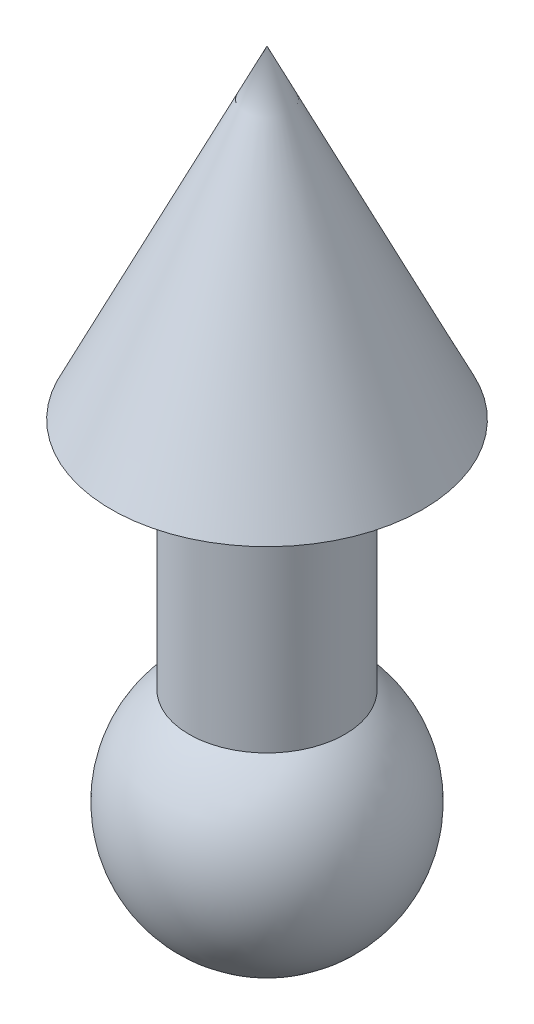
SolidWorks part; units mm, degrees
ref_plane "Front" through (0, 0, 0) normal (0, 0, 1) x (1, 0, 0)
ref_plane "Top" through (0, 0, 0) normal (0, 1, 0) x (1, 0, 0)
ref_plane "Right" through (0, 0, 0) normal (1, 0, 0) x (0, 0, -1)
sketch "Sketch1" plane through (0, 0, 0) normal (0, 0, 1) x (1, 0, 0)
  line L0 (5, 21.245) -> (5, 6.245)
  line L1 (5, 21.245) -> (10, 21.245)
  line L2 (10, 21.245) -> (0, 42)
  line L3 (0, -55) -> (0, 55) construction
  line L4 (0, 42) -> (0, -8)
  arc A0 (0, -8) -> (5, 6.245) centre (0, 0) ccw
  point P1 (0, 66.0713)
  point P5 (5, 43.4956)
  point P11 (11.2879, 43.4956)
  point P12 (0, 49.4458)
  dimension "D1" = 8
  dimension "D2" = 5
  dimension "D3" = 15
  dimension "D4" = 5
  dimension "D5" = 50
revolve "Revolve1" add sketch "Sketch1" angle 360 about L4
ref_axis "Axis1" through (0, 67.4322, 0) along (0, -1, 0)
